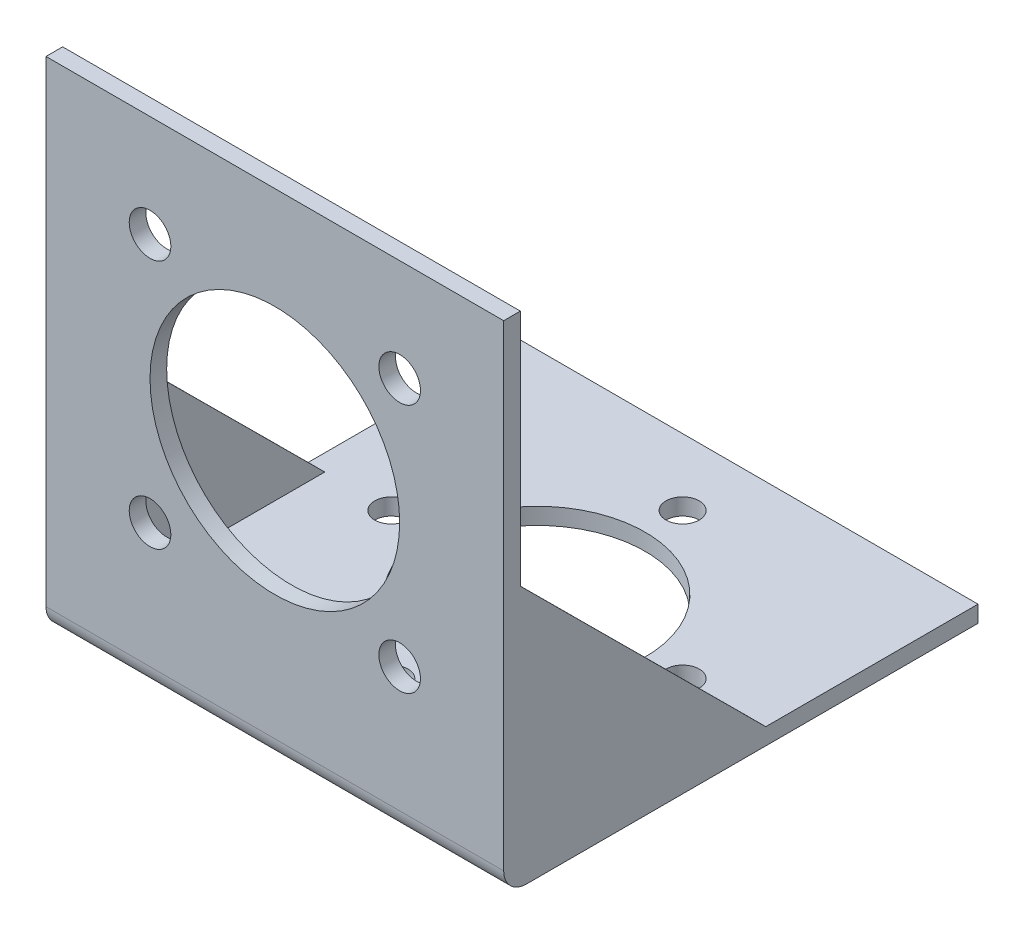
SolidWorks part; units mm, degrees
note: The reader was unsure of these and kept them because the rebuilt part matched: flange length of "边线-法兰1".
material "AISI 304"
ref_plane "前视基准面" through (0, 0, 0) normal (0, 0, 1) x (1, 0, 0)
ref_plane "上视基准面" through (0, 0, 0) normal (0, 1, 0) x (1, 0, 0)
ref_plane "右视基准面" through (0, 0, 0) normal (1, 0, 0) x (0, 0, -1)
sketch "草图1" plane through (0, 0, 0) normal (0, 1, 0) x (1, 0, 0)
  line L1 (-27.5, 25.5) -> (27.5, 25.5)
  line L2 (-27.5, 25.5) -> (-27.5, -29.5)
  line L3 (-27.5, -29.5) -> (27.5, -29.5)
  line L4 (27.5, 25.5) -> (27.5, -29.5)
  line L5 (-27.5, 25.5) -> (27.5, -29.5) construction
  line L6 (-27.5, -29.5) -> (27.5, 25.5) construction
  circle A0 centre (0, 0) radius 13
  circle A1 centre (0, 0) radius 17.5 construction
  circle A2 centre (17.5, 0) radius 2
  circle A3 centre (-17.5, 0) radius 2
  circle A4 centre (0, 17.5) radius 2
  circle A5 centre (0, -17.5) radius 2
  point P23 (0, -2)
  dimension "D1" = 26
  dimension "D2" = 35
  dimension "D3" = 4
  dimension "D4" = 8
  dimension "D5" = 4
  dimension "D6" = 12
  dimension "D7" = 10
base flange "基体-法兰1" sketch "草图1" thickness 2 reverse thickness direction no parameters "D1"=0.7366
edge flange "边线-法兰1" sketch "草图8" flange angle 90 flange length 60 flange position material outside bend radius 0.7366 thickness 2 relief rectangular parameters "D6"=10
sketch "草图8" plane through (0, 0, 29.5) normal (0, 0, 1) x (1, 0, 0)
  line L0 (-27.5, 0) -> (27.5, 0) construction
  line L1 (-27.5, 0) -> (27.5, 0)
  line L2 (-27.5, 0) -> (-27.5, 58)
  line L3 (-27.5, 58) -> (27.5, 58)
  line L4 (27.5, 58) -> (27.5, 0)
bend "边线折弯1" bend radius 0.7366 bend angle 90 parameters "D5"=1
sketch "草图9" plane through (0, 0, 29.5) normal (0, 0, -1) x (-1, 0, 0)
  line L0 (-49.1656, 30.7366) -> (65.3821, 30.7366) construction
  line L1 (0, 60.8016) -> (0, -15.7109) construction
  line L2 (27.5, 0.7366) -> (-27.5, 0.7366) construction
  circle A0 centre (0, 30.7366) radius 15
  circle A1 centre (-15, 45.7366) radius 2.5
  circle A2 centre (-15, 15.7366) radius 2.5
  circle A3 centre (15, 15.7366) radius 2.5
  circle A4 centre (15, 45.7366) radius 2.5
  dimension "D1" = 30
  dimension "D2" = 30
  dimension "D4" = 5
  dimension "D3" = 30
  dimension "D5" = 15
extrude "切除-拉伸1" cut sketch "草图9" against normal blind 10
sketch "草图10" plane through (27.5, 0, 0) normal (1, 0, 0) x (0, 0, -1)
  line L0 (-29.5, 29.3683) -> (0, 0)
  line L1 (-29.5, 0.7366) -> (-29.5, 58) construction
  line L2 (-29.5, 29.3683) -> (-29.5, 0)
  line L3 (0, 0) -> (-29.5, 0)
extrude "凸台-拉伸1" add sketch "草图10" against normal blind 2
sketch "草图11" plane through (-27.5, 0, 0) normal (-1, 0, 0) x (0, 0, 1)
  line L0 (29.5, 29.3683) -> (0, 0)
  line L1 (0, 0) -> (29.5, 0)
  line L2 (29.5, 29.3683) -> (29.5, 0)
extrude "凸台-拉伸2" add sketch "草图11" against normal blind 2
sketch "折弯-线1" [suppressed] plane through (0, 0, 0) normal (0, 1, 0) x (1, 0, 0)
sketch "边界框1" [suppressed] plane through (0, 0, 0) normal (0, 1, 0) x (1, 0, 0)
sheet metal parameters "钣金1" thickness 2 parameters "D1"=0.7366
flat pattern "平板型式1" [suppressed]
sketch "折弯-线2" plane through (0, 0, 0) normal (0, 1, 0) x (1, 0, 0)
sketch3d "边界框2" [suppressed]
  line L0 (27.5, 25.5, 0) -> (27.5, -29.5, 0) construction
  line L1 (-27.5, 25.5, 0) -> (-27.5, -29.5, 0) construction
  line L2 (27.5, 25.5, 0) -> (-27.5, 25.5, 0) construction
  line L3 (27.5, -29.5, 0) -> (-27.5, -29.5, 0) construction
sheet metal parameters "钣金2" thickness 2 parameters "D1"=0.7366
flat pattern "平板型式1"
sketch "折弯-线2" plane through (0, 0, 0) normal (0, 1, 0) x (1, 0, 0)
  line L0 (-27.5, -30.1273) -> (27.5, -30.1273) construction
  line L1 (-27.5, -30.1273) -> (27.5, -30.1273) construction
sketch3d "边界框2" [suppressed]
  line L0 (-27.5, 25.5, 0) -> (-27.5, -88.7546, 0) construction
  line L1 (27.5, 25.5, 0) -> (27.5, -88.7546, 0) construction
  line L2 (-27.5, 25.5, 0) -> (27.5, 25.5, 0) construction
  line L3 (-27.5, -88.7546, 0) -> (27.5, -88.7546, 0) construction
bend of the flat pattern "展开-<边线折弯1>1"
sheet metal parameters "钣金3" thickness 2 parameters "D1"=0.7366
flat pattern "平板型式1"
sketch "折弯-线2" plane through (0, 0, 0) normal (0, 1, 0) x (1, 0, 0)
  line L0 (-27.5, -30.1273) -> (27.5, -30.1273) construction
  line L1 (-27.5, -30.1273) -> (27.5, -30.1273) construction
sketch3d "边界框2" [suppressed]
  line L0 (-27.5, 25.5, 0) -> (-27.5, -88.7546, 0) construction
  line L1 (27.5, 25.5, 0) -> (27.5, -88.7546, 0) construction
  line L2 (-27.5, 25.5, 0) -> (27.5, 25.5, 0) construction
  line L3 (-27.5, -88.7546, 0) -> (27.5, -88.7546, 0) construction
bend of the flat pattern "展开-<边线折弯1>1"
sheet metal parameters "钣金4" thickness 2 parameters "D1"=0.7366
flat pattern "平板型式1"
sketch "折弯-线2" plane through (0, 0, 0) normal (0, 1, 0) x (1, 0, 0)
  line L0 (-27.5, -30.1273) -> (27.5, -30.1273) construction
  line L1 (-27.5, -30.1273) -> (27.5, -30.1273) construction
sketch3d "边界框2" [suppressed]
  line L0 (-27.5, 25.5, 0) -> (-27.5, -88.7546, 0) construction
  line L1 (27.5, 25.5, 0) -> (27.5, -88.7546, 0) construction
  line L2 (-27.5, 25.5, 0) -> (27.5, 25.5, 0) construction
  line L3 (-27.5, -88.7546, 0) -> (27.5, -88.7546, 0) construction
bend of the flat pattern "展开-<边线折弯1>1"
sheet metal parameters "钣金5" thickness 2 parameters "D1"=0.7366
flat pattern "平板型式1"
sketch "折弯-线2" plane through (0, 0, 0) normal (0, 1, 0) x (1, 0, 0)
  line L0 (-27.5, -30.1273) -> (27.5, -30.1273) construction
  line L1 (-27.5, -30.1273) -> (27.5, -30.1273) construction
sketch3d "边界框2" [suppressed]
  line L0 (-27.5, 25.5, 0) -> (-27.5, -88.7546, 0) construction
  line L1 (27.5, 25.5, 0) -> (27.5, -88.7546, 0) construction
  line L2 (-27.5, 25.5, 0) -> (27.5, 25.5, 0) construction
  line L3 (-27.5, -88.7546, 0) -> (27.5, -88.7546, 0) construction
bend of the flat pattern "展开-<边线折弯1>1"
